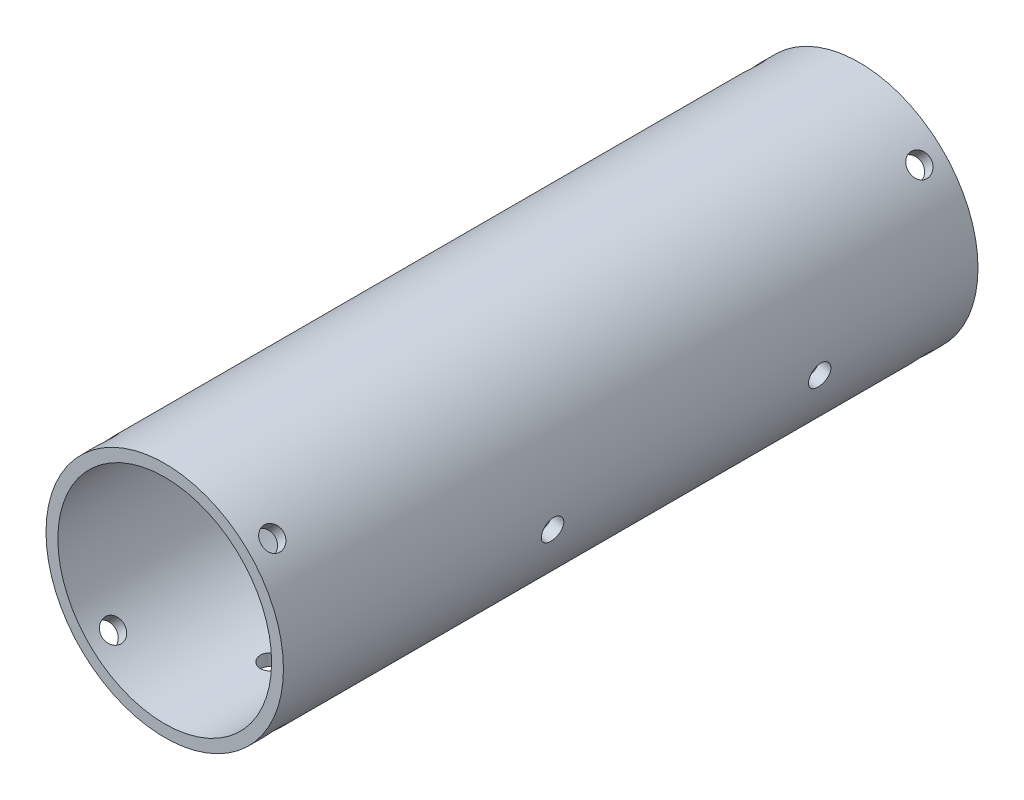
SolidWorks part; units mm, degrees
material "PET"
ref_plane "Front Plane" through (0, 0, 0) normal (0, 0, 1) x (1, 0, 0)
ref_plane "Top Plane" through (0, 0, 0) normal (0, 1, 0) x (1, 0, 0)
ref_plane "Right Plane" through (0, 0, 0) normal (1, 0, 0) x (0, 0, -1)
sketch "Sketch1" plane through (0, 0, 0) normal (0, 0, 1) x (1, 0, 0)
  circle A0 centre (0, 0) radius 20
  circle A1 centre (0, 0) radius 18
  dimension "D1" = 40
  dimension "D2" = 2
extrude "Boss-Extrude1" add sketch "Sketch1" along normal blind 100
ref_plane "Plane1" through (-19.6962, -3.473, 0) normal (-0.9848, -0.1736, 0) x (0, 0, -1)
sketch "Sketch3" plane through (-19.6962, -3.473, 0) normal (-0.9848, -0.1736, 0) x (0, 0, -1)
  line L0 (-100, 20) -> (-100, -20) construction
  line L2 (0, -20) -> (0, 20) construction
  line L5 (-72.5, -5.4687) -> (-7.5, -5.4687) construction
  circle A0 centre (-62.5, -0.9687) radius 1.875
  circle A1 centre (-17.5, -0.9687) radius 1.875
  dimension "D1" = 3.75
  dimension "D5" = 4.5
  dimension "D2" = 37.5
  dimension "D3" = 17.5
  dimension "D4" = 2
extrude "Cut-Extrude1" cut sketch "Sketch3" against normal up to surface (2.0228 mm away) up to face at (18, 0, 100)
mirror "Mirror1" about plane through (0, 0, 0) normal (1, 0, 0) of "Cut-Extrude1"
sketch "Sketch4" plane through (0, 0, 0) normal (0, 1, 0) x (1, 0, 0)
  line L0 (-20, -100) -> (20, -100) construction
  circle A0 centre (0, -90) radius 1.875
  dimension "D1" = 3.75
  dimension "D2" = 10
extrude "Cut-Extrude2" cut sketch "Sketch4" against normal blind 23
sketch "Sketch5" plane through (0, 0, 0) normal (0, 0, -1) x (-1, 0, 0)
  circle A0 centre (0, 0) radius 18
  circle A1 centre (0, 0) radius 20
  dimension "D1" = 2
extrude "Boss-Extrude2" add sketch "Sketch5" along normal blind 9
sketch "Sketch6" plane through (0, 0, 100) normal (0, 0, 1) x (1, 0, 0)
  circle A0 centre (0, 0) radius 18
  circle A1 centre (0, 0) radius 20
  dimension "D1" = 2
extrude "Boss-Extrude3" add sketch "Sketch6" along normal blind 8
ref_plane "Plane2" through (-14.1421, -14.1421, 0) normal (-0.7071, -0.7071, 0) x (0, 0, -1)
sketch "Sketch7" plane through (-14.1421, -14.1421, 0) normal (-0.7071, -0.7071, 0) x (0, 0, -1)
  line L0 (-108, 20) -> (-108, -20) construction
  circle A0 centre (-104, 0) radius 1.875
  dimension "D1" = 3.75
  dimension "D2" = 4
extrude "Cut-Extrude3" cut sketch "Sketch7" against normal up to next
pattern_circular "CirPattern1" count 4 over 360 about axis through (0, 0, 100) along (0, 0, -1) of "Cut-Extrude3"
ref_plane "Plane3" through (0, 0, 49.5) normal (0, 0, 1) x (1, 0, 0)
mirror "Mirror2" about plane through (0, 0, 49.5) normal (0, 0, 1) of "CirPattern1", "Cut-Extrude3"
